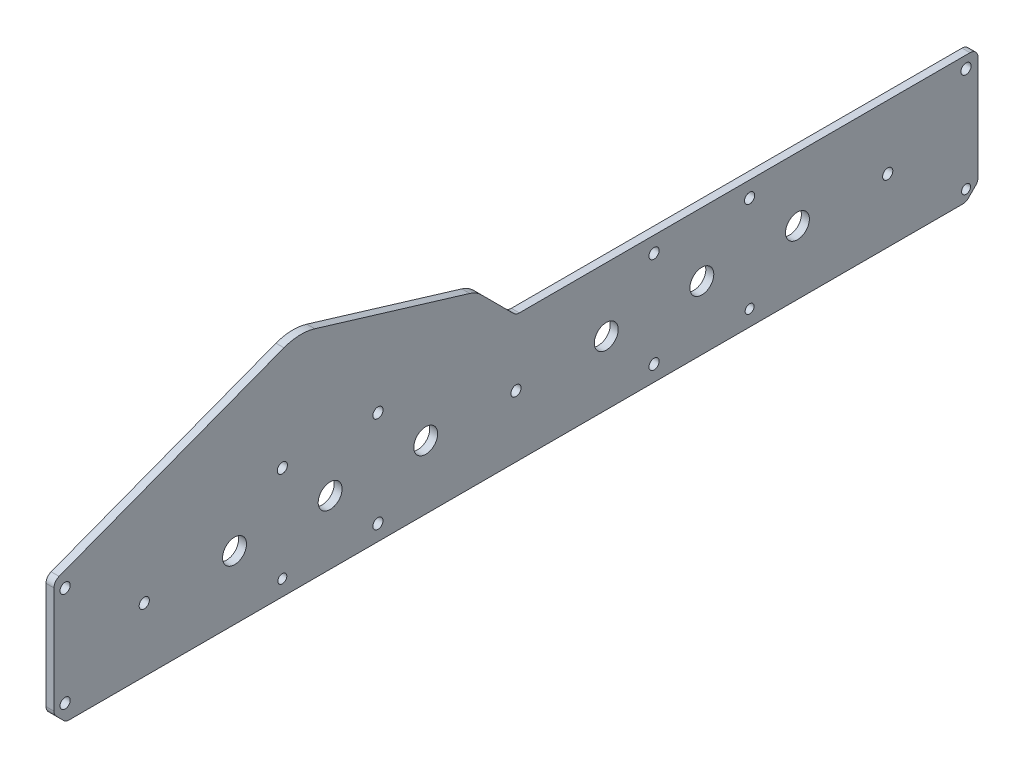
SolidWorks part; units mm, degrees
ref_plane "Front Plane" through (0, 0, 0) normal (0, 0, 1) x (1, 0, 0)
ref_plane "Top Plane" through (0, 0, 0) normal (0, 1, 0) x (1, 0, 0)
ref_plane "Right Plane" through (0, 0, 0) normal (1, 0, 0) x (0, 0, -1)
sketch "Sketch1" plane through (0, 0, 0) normal (1, 0, 0) x (0, 0, -1)
  line L0 (-184.15, 26.1937) -> (-92.4839, 61.0534)
  line L1 (-184.15, -24.6062) -> (184.15, -24.6062)
  line L2 (-184.15, -24.6062) -> (-184.15, 26.1937)
  line L3 (0, 26.1937) -> (184.15, 26.1937)
  line L4 (184.15, -24.6062) -> (184.15, 26.1937)
  line L5 (-80.1935, 61.4805) -> (-18.395, 42.7743)
  line L6 (-13.8706, 40.0644) -> (0, 26.1937)
  arc A0 (-92.4839, 61.0534) -> (-80.1935, 61.4805) centre (-85.7125, 43.2475) cw
  arc A1 (-18.395, 42.7743) -> (-13.8706, 40.0644) centre (-21.5354, 32.3996) cw
  circle A2 centre (-25.1593, 30.6938) radius 2.032 construction
  circle A3 centre (-21.5354, 32.3996) radius 1.905 construction
  point P6 (0, -24.6062)
  dimension "D4" = 19.05
  dimension "D1" = 50.8
  dimension "D2" = 368.3
  dimension "D3" = 24.6062
  dimension "D5" = 45
extrude "Boss-Extrude1" add sketch "Sketch1" along normal blind 3.175
chamfer "Chamfer1" distance 4.7625 angle 45 2 edges at (1.5875, -24.6062, -184.15) (1.5875, -24.6062, 184.15)
fillet "Fillet1" radius 3.175 7 edges at (1.5875, -24.6062, -179.3875) (1.5875, -19.8437, -184.15) (1.5875, 26.1937, -184.15) (1.5875, -24.6062, 179.3875) (1.5875, -19.8437, 184.15) (1.5875, 26.1937, 0) (1.5875, 26.1937, 184.15)
sketch "Sketch4" plane through (3.175, 0, 0) normal (1, 0, 0) x (0, 0, -1)
  point P0 (-93.1246, 19.9098)
  point P1 (-55.0246, 19.9098)
  point P3 (0, 0)
  point P5 (55.0246, 19.9098)
  point P7 (93.1246, 19.9098)
  point P9 (55.0246, -18.3223)
  point P11 (-55.0246, -18.3223)
  point P13 (-179.705, 21.7487)
  point P15 (-179.705, -18.0026)
  point P17 (179.3875, 21.4312)
  point P19 (148.1579, 0.7938)
  point P21 (-148.1579, 0.7937)
hole_wizard "#8 Clearance Hole1" positions "Sketch4" profile "Sketch5" hole size "#8" standard "ANSI Inch" end condition up to next
sketch "Sketch5" plane through (3.175, 19.9098, 93.1246) normal (0, 1, 0) x (0, 0, -1)
  line L0 (0, 0) -> (0, 3.175)
  line L1 (0, 3.175) -> (2.032, 3.175)
  line L2 (2.032, 3.175) -> (2.032, 0)
  line L5 (2.032, 0) -> (0, 0)
  line L11 (0, -6.35) -> (0, 107.95) construction
  dimension "Thru Hole Dia." = 4.064
  dimension "Thru Hole Depth" = 3.175
sketch "Sketch6" plane through (3.175, 0, 0) normal (1, 0, 0) x (0, 0, -1)
  point P0 (-93.1246, -18.3223)
  point P1 (93.1246, -18.3223)
  point P3 (179.3875, -20.1161)
hole_wizard "#8 Clearance Hole2" positions "Sketch6" profile "Sketch7" hole size "#8" standard "ANSI Inch" end condition up to next
sketch "Sketch7" plane through (3.175, -18.3223, 93.1246) normal (0, 1, 0) x (0, 0, -1)
  line L0 (0, 0) -> (0, 3.175)
  line L1 (0, 3.175) -> (1.778, 3.175)
  line L2 (1.778, 3.175) -> (1.778, 0)
  line L5 (1.778, 0) -> (0, 0)
  line L11 (0, -6.35) -> (0, 107.95) construction
  dimension "Thru Hole Dia." = 3.556
  dimension "Thru Hole Depth" = 3.175
sketch "Sketch8" plane through (3.175, 0, 0) normal (1, 0, 0) x (0, 0, -1)
  point P0 (-112.1746, 0.7937)
  point P1 (-74.0746, 0.7938)
  point P3 (-35.9746, 0.7938)
  point P5 (35.9746, 0.7938)
  point P7 (74.0746, 0.7937)
  point P9 (112.1746, 0.7937)
hole_wizard "3/8 Clearance Hole1" positions "Sketch8" profile "Sketch9" hole size "3/8" standard "ANSI Inch" end condition up to next
sketch "Sketch9" plane through (3.175, 0.7937, 112.1746) normal (0, 1, 0) x (0, 0, -1)
  line L0 (0, 0) -> (0, 3.175)
  line L1 (0, 3.175) -> (4.7625, 3.175)
  line L2 (4.7625, 3.175) -> (4.7625, 0)
  line L5 (4.7625, 0) -> (0, 0)
  line L11 (0, -6.35) -> (0, 107.95) construction
  dimension "Thru Hole Dia." = 9.525
  dimension "Thru Hole Depth" = 3.175
